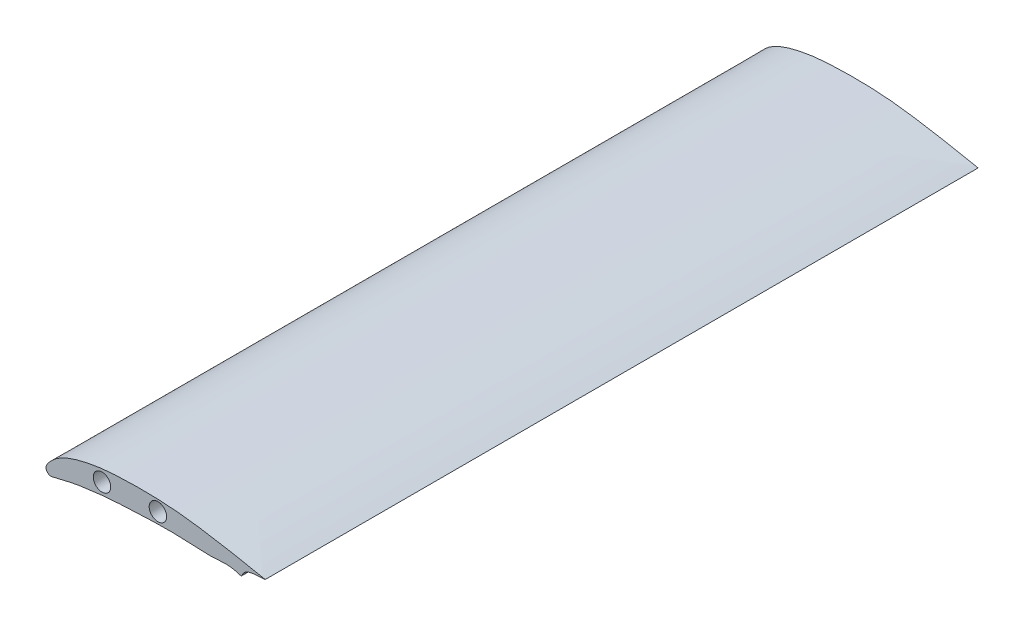
SolidWorks part; units mm, degrees
ref_plane "Front Plane" through (0, 0, 0) normal (0, 0, 1) x (1, 0, 0)
ref_plane "Top Plane" through (0, 0, 0) normal (0, 1, 0) x (1, 0, 0)
ref_plane "Right Plane" through (0, 0, 0) normal (1, 0, 0) x (0, 0, -1)
curve "cut"
  spline degree 3 poles (23.4129, 1.6732, 0) (26.2385, 1.4563, 0) (24.6666, 1.7296, 0) (24.0631, 1.8554, 0) (23.3676, 1.991, 0) (21.8468, 2.2963, 0) (19.449, 2.7181, 0) (16.2072, 3.2214, 0) (12.9484, 3.4695, 0) (9.6969, 3.4728, 0) (6.9821, 3.3475, 0) (4.8205, 2.9999, 0) (3.4681, 2.6661, 0) (2.3898, 2.2791, 0) (1.5621, 1.8808, 0) (0.8771, 1.387, 0) (0.3211, 0.7955, 0) (-0.2215, 0.1147, 0) (0.3268, -0.5439, 0) (0.9664, -0.4072, 0) (1.6227, -0.2531, 0) (2.4342, -0.0542, 0) (3.5055, 0.1899, 0) (4.8628, 0.367, 0) (7.0187, 0.6467, 0) (9.7247, 0.7989, 0) (12.9785, 0.9423, 0) (16.1932, 0.9351, 0) (19.4533, 0.6426, 0) (21.3272, 1.0151, 0) (22.681, 0.4934, 0) (22.872, 0.9133, 0) (23.4129, 1.6732, 0) (26.2385, 1.4563, 0) (24.6666, 1.7296, 0) knots -0.057358 -0.055858 -0.038892 0 0.013065 0.026125 0.039194 0.052259 0.114884 0.177154 0.238899 0.300426 0.362024 0.393129 0.424785 0.441092 0.458148 0.477061 0.488021 0.506046 0.517777 0.525474 0.541223 0.556994 0.572703 0.603759 0.634701 0.696322 0.75786 0.819389 0.880956 0.936472 0.942642 0.944142 0.961108 1 1.013065 1.026125 1.039194 periodic
sketch "cut sketch" plane through (0, 0, 0) normal (0, 0, 1) x (1, 0, 0)
  line L0 (0, 0) -> (19.8755, 0) construction
  line L1 (19.8755, 0) -> (19.8755, 1.2434) construction
  line L2 (9.9377, 0) -> (9.9377, 2.69) construction
  line L3 (198.755, 0) -> (198.755, 12.4341) construction
  line L4 (0, 0) -> (198.755, 0) construction
  line L5 (99.3775, 0) -> (99.3775, 26.9) construction
  line L6 (50.8, 0) -> (50.8, 4.4202) construction
  line L7 (50.8, 4.4202) -> (50.8, 25.4008) construction
  line L8 (101.6, 0) -> (101.6, 7.179) construction
  line L9 (101.6, 7.179) -> (101.6, 26.8197) construction
  circle A0 centre (50.8, 14.9105) radius 7.9375
  circle A1 centre (101.6, 16.9993) radius 7.9375
  spline S0 degree 3 poles (183.2058, 13.0927) (205.3166, 11.3957) (193.0163, 13.5342) (188.2941, 14.5185) (182.8517, 15.5792) (170.9511, 17.9689) (152.1886, 21.2695) (126.8211, 25.2077) (101.3214, 27.1488) (75.8786, 27.1749) (54.6349, 26.194) (37.7206, 23.4738) (27.1378, 20.8625) (18.6998, 17.8336) (12.2233, 14.7175) (6.8632, 10.853) (2.5126, 6.2248) (-1.7331, 0.8973) (2.5575, -4.2564) (7.562, -3.1865) (12.6976, -1.9802) (19.0475, -0.4243) (27.4305, 1.4859) (38.0511, 2.872) (54.9212, 5.0608) (76.096, 6.2515) (101.5566, 7.3732) (126.7117, 7.3174) (152.222, 5.0287) (166.8852, 7.9435) (177.4789, 3.8608) (178.9732, 7.1462) (183.2058, 13.0927) (205.3166, 11.3957) (193.0163, 13.5342) knots -0.057358 -0.055858 -0.038892 0 0.013065 0.026125 0.039194 0.052259 0.114884 0.177154 0.238899 0.300426 0.362024 0.393129 0.424785 0.441092 0.458148 0.477061 0.488021 0.506046 0.517777 0.525474 0.541223 0.556994 0.572703 0.603759 0.634701 0.696322 0.75786 0.819389 0.880956 0.936472 0.942642 0.944142 0.961108 1 1.013065 1.026125 1.039194 only from (198.755, 12.4341) to (198.755, 12.4341)
  spline S2 degree 3 poles (18.3206, 1.3093) (20.5317, 1.1396) (19.3016, 1.3534) (18.8294, 1.4518) (18.2852, 1.5579) (17.0951, 1.7969) (15.2189, 2.1269) (12.6821, 2.5208) (10.1321, 2.7149) (7.5879, 2.7175) (5.4635, 2.6194) (3.7721, 2.3474) (2.7138, 2.0862) (1.87, 1.7834) (1.2223, 1.4718) (0.6863, 1.0853) (0.2513, 0.6225) (-0.1733, 0.0897) (0.2558, -0.4256) (0.7562, -0.3186) (1.2698, -0.198) (1.9047, -0.0424) (2.743, 0.1486) (3.8051, 0.2872) (5.4921, 0.5061) (7.6096, 0.6252) (10.1557, 0.7373) (12.6712, 0.7317) (15.2222, 0.5029) (16.6885, 0.7944) (17.7479, 0.3861) (17.8973, 0.7146) (18.3206, 1.3093) (20.5317, 1.1396) (19.3016, 1.3534) knots -0.057358 -0.055858 -0.038892 0 0.013065 0.026125 0.039194 0.052259 0.114884 0.177154 0.238899 0.300426 0.362024 0.393129 0.424785 0.441092 0.458148 0.477061 0.488021 0.506046 0.517777 0.525474 0.541223 0.556994 0.572703 0.603759 0.634701 0.696322 0.75786 0.819389 0.880956 0.936472 0.942642 0.944142 0.961108 1 1.013065 1.026125 1.039194 only from (19.8755, 1.2434) to (19.8755, 1.2434) construction
  point P11 (50.8, 0)
  point P17 (101.6, 0)
  point P20 (101.6, 16.9993)
  dimension "D8" = 15.875
  dimension "D10" = 15.875
  dimension "D1" = 1.2434
  dimension "D2" = 19.8755
  dimension "D3" = 2.69
  dimension "D4" = 198.755
  dimension "D5" = 12.4341
  dimension "D6" = 26.9
  dimension "D7" = 50.8
  dimension "D9" = 50.8
curve "full"
  spline degree 3 poles (25.4, 0.0889, 0) (24.9755, 0.1879, 0) (24.1284, 0.3854, 0) (22.4316, 0.7474, 0) (20.3056, 1.1527, 0) (17.7661, 1.6728, 0) (15.2225, 2.1285, 0) (12.6828, 2.5208, 0) (10.1333, 2.7153, 0) (7.5886, 2.7177, 0) (5.4641, 2.6194, 0) (3.7724, 2.3478, 0) (2.7142, 2.0863, 0) (1.8702, 1.7836, 0) (1.2225, 1.4719, 0) (0.6864, 1.0854, 0) (0.2512, 0.6226, 0) (-0.1733, 0.0898, 0) (0.2557, -0.4257, 0) (0.7562, -0.3188, 0) (1.2698, -0.1979, 0) (1.905, -0.0426, 0) (2.7433, 0.1487, 0) (3.8055, 0.2872, 0) (5.4925, 0.5064, 0) (7.6119, 0.6227, 0) (10.1512, 0.7472, 0) (12.6929, 0.6952, 0) (15.2354, 0.6324, 0) (17.7755, 0.4534, 0) (20.3173, 0.2785, 0) (22.4335, 0.1017, 0) (24.1313, 0.0327, 0) (24.9769, -0.0484, 0) (25.4, -0.0889, 0) knots 0 0 0 0 0.025045 0.049982 0.099693 0.149405 0.198931 0.248178 0.297011 0.345669 0.394384 0.418982 0.444018 0.456913 0.470405 0.485361 0.494029 0.508284 0.517562 0.523649 0.536105 0.548579 0.561002 0.585562 0.610033 0.658766 0.707435 0.756094 0.804785 0.853571 0.902386 0.951201 0.975578 1 1 1 1
sketch "full foil sketch" plane through (0, 0, 0) normal (0, 0, 1) x (1, 0, 0)
  line L0 (25.4, 0.0889) -> (25.4, -0.0889)
  spline S0 degree 3 poles (801.0896, 2896.6153) (93.9918, -50.1126) (62.4745, -7.7955) (22.4316, 0.7474) (20.3056, 1.1527) (17.7661, 1.6728) (15.2225, 2.1285) (12.6828, 2.5208) (10.1333, 2.7153) (7.5886, 2.7177) (5.4641, 2.6194) (3.7724, 2.3478) (2.7142, 2.0863) (1.8702, 1.7836) (1.2225, 1.4719) (0.6864, 1.0854) (0.2512, 0.6226) (-0.1733, 0.0898) (0.2557, -0.4257) (0.7562, -0.3188) (1.2698, -0.1979) (1.905, -0.0426) (2.7433, 0.1487) (3.8055, 0.2872) (5.4925, 0.5064) (7.6119, 0.6227) (10.1512, 0.7472) (12.6929, 0.6952) (15.2354, 0.6324) (17.7755, 0.4534) (20.3173, 0.2785) (22.4335, 0.1017) (51.136, -1.0652) (75.492, -52.2811) (315.1102, 2985.1217) knots -2.25291 -2.25291 -2.25291 -2.25291 0.025045 0.049982 0.099693 0.149405 0.198931 0.248178 0.297011 0.345669 0.394384 0.418982 0.444018 0.456913 0.470405 0.485361 0.494029 0.508284 0.517562 0.523649 0.536105 0.548579 0.561002 0.585562 0.610033 0.658766 0.707435 0.756094 0.804785 0.853571 0.902386 0.951201 0.975578 2.552608 2.552608 2.552608 2.552608 only from (25.4, 0.0889) to (25.4, -0.0889) construction
  spline S1 degree 3 poles (25.4, 0.0889) (24.9755, 0.1879) (24.1284, 0.3854) (22.4316, 0.7474) (20.3056, 1.1527) (17.7661, 1.6728) (15.2225, 2.1285) (12.6828, 2.5208) (10.1333, 2.7153) (7.5886, 2.7177) (5.4641, 2.6194) (3.7724, 2.3478) (2.7142, 2.0863) (1.8702, 1.7836) (1.2225, 1.4719) (0.6864, 1.0854) (0.2512, 0.6226) (-0.1733, 0.0898) (0.2557, -0.4257) (0.7562, -0.3188) (1.2698, -0.1979) (1.905, -0.0426) (2.7433, 0.1487) (3.8055, 0.2872) (5.4925, 0.5064) (7.6119, 0.6227) (10.1512, 0.7472) (12.6929, 0.6952) (15.2354, 0.6324) (17.7755, 0.4534) (20.3173, 0.2785) (22.4335, 0.1017) (24.1313, 0.0327) (24.9769, -0.0484) (25.4, -0.0889) knots 0 0 0 0 0.025045 0.049982 0.099693 0.149405 0.198931 0.248178 0.297011 0.345669 0.394384 0.418982 0.444018 0.456913 0.470405 0.485361 0.494029 0.508284 0.517562 0.523649 0.536105 0.548579 0.561002 0.585562 0.610033 0.658766 0.707435 0.756094 0.804785 0.853571 0.902386 0.951201 0.975578 1 1 1 1
extrude "Boss-Extrude1" add sketch "cut sketch" along normal blind 647.7
ref_plane "Plane1" through (0, 0, 323.85) normal (0, 0, 1) x (1, 0, 0)
ref_plane "Plane2" through (0, 0, 485.775) normal (0, 0, 1) x (1, 0, 0)
ref_plane "Plane3" through (0, 0, 161.925) normal (0, 0, 1) x (1, 0, 0)
sketch "Sketch1" plane through (0, 0, 323.85) normal (0, 0, 1) x (1, 0, 0)
  line L0 (177.2281, 4.2649) -> (177.2281, -23.5227) construction
  line L1 (177.2281, -23.5227) -> (184.8481, -23.5227) construction
  circle A0 centre (184.8481, -23.5227) radius 1.27
  spline S0 degree 3 poles (183.2058, 13.0927) (205.3166, 11.3957) (193.0163, 13.5342) (188.2941, 14.5185) (182.8517, 15.5792) (170.9511, 17.9689) (152.1886, 21.2695) (126.8211, 25.2077) (101.3214, 27.1488) (75.8786, 27.1749) (54.6349, 26.194) (37.7206, 23.4738) (27.1378, 20.8625) (18.6998, 17.8336) (12.2233, 14.7175) (6.8632, 10.853) (2.5126, 6.2248) (-1.7331, 0.8973) (2.5575, -4.2564) (7.562, -3.1865) (12.6976, -1.9802) (19.0475, -0.4243) (27.4305, 1.4859) (38.0511, 2.872) (54.9212, 5.0608) (76.096, 6.2515) (101.5566, 7.3732) (126.7117, 7.3174) (152.222, 5.0287) (166.8852, 7.9435) (177.4789, 3.8608) (178.9732, 7.1462) (183.2058, 13.0927) (205.3166, 11.3957) (193.0163, 13.5342) knots -0.057358 -0.055858 -0.038892 0 0.013065 0.026125 0.039194 0.052259 0.114884 0.177154 0.238899 0.300426 0.362024 0.393129 0.424785 0.441092 0.458148 0.477061 0.488021 0.506046 0.517777 0.525474 0.541223 0.556994 0.572703 0.603759 0.634701 0.696322 0.75786 0.819389 0.880956 0.936472 0.942642 0.944142 0.961108 1 1.013065 1.026125 1.039194 only from (198.755, 12.4341) to (198.755, 12.4341) construction
  point P0 (177.2281, 4.2649)
  dimension "D3" = 2.54
  dimension "D1" = 27.7876
  dimension "D2" = 7.62
